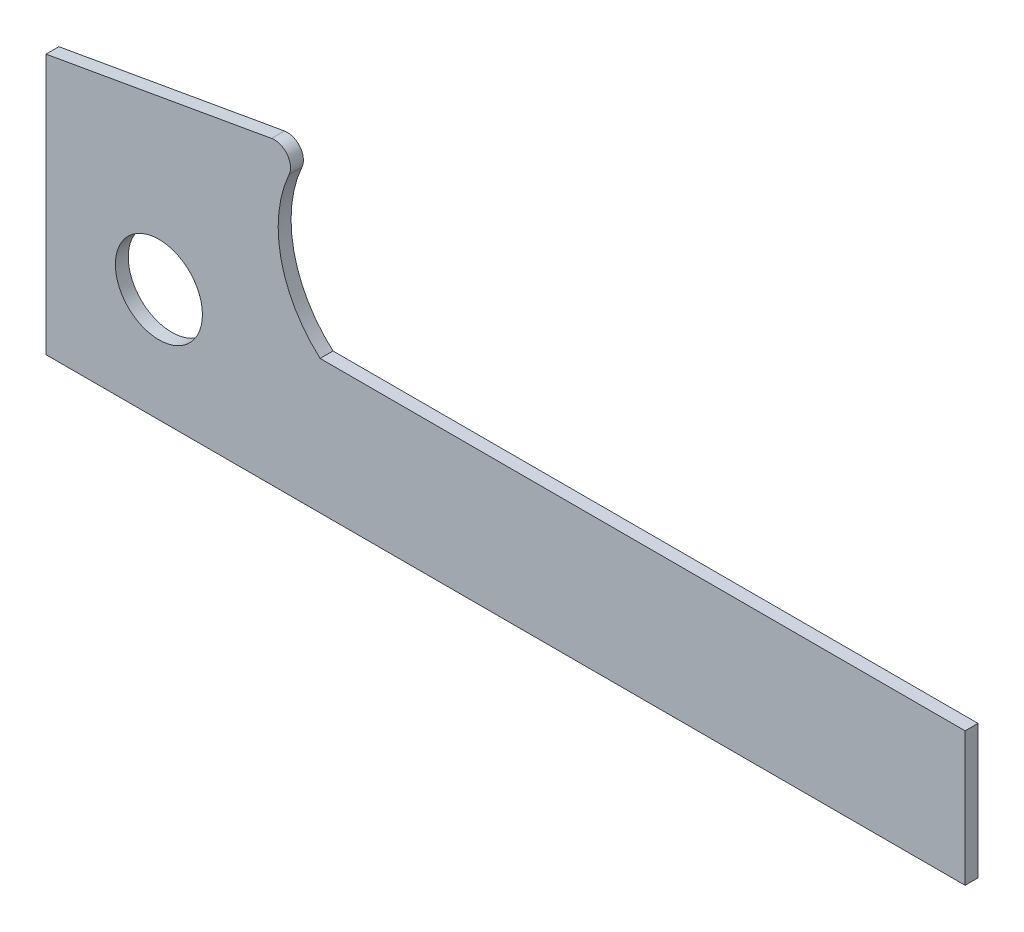
SolidWorks part; units mm, degrees
material "AISI 1020"
ref_plane "Спереди" through (0, 0, 0) normal (0, 0, 1) x (1, 0, 0)
ref_plane "Сверху" through (0, 0, 0) normal (0, 1, 0) x (1, 0, 0)
ref_plane "Справа" through (0, 0, 0) normal (1, 0, 0) x (0, 0, -1)
sketch "Эскиз1" plane through (0, 0, 0) normal (0, 0, 1) x (1, 0, 0)
  line L0 (0, -35) -> (0, 35) construction
  line L1 (0, -35) -> (250, -35)
  line L2 (-35, -35) -> (-35, 45.7214)
  line L4 (250, -35) -> (250, 6.5)
  line L5 (0, 0) -> (40.5631, 44.0234) construction
  line L6 (-17.2764, -30.4389) -> (17.2764, 30.4389) construction
  line L8 (-35, -35) -> (-35, -40) construction
  line L9 (-35, -40) -> (250, -40) construction
  line L10 (250, -40) -> (250, -35) construction
  line L12 (-35, -35) -> (0, -35)
  line L13 (200.1444, -153.8415) -> (-17.2764, -30.4389) construction
  line L14 (58.4892, 12.7455) -> (43.6208, 25) construction
  line L15 (43.6208, 25) -> (40.5631, 44.0234) construction
  line L16 (0, 0) -> (58.4892, 12.7455) construction
  line L17 (0, 0) -> (43.6208, 25) construction
  line L18 (0, 0) -> (43.6208, 25) construction
  line L19 (50, 6.5) -> (110, 6.5) construction
  line L20 (-35, 45.7214) -> (34.9487, 58.0553)
  line L21 (-1450, 65) -> (100, 65) construction
  line L22 (50, 6.5) -> (250, 6.5)
  circle A0 centre (40.5631, 44.0234) radius 2.5 construction
  circle A1 centre (43.6208, 25) radius 2.5 construction
  arc A2 (50, 6.5) -> (40.3761, 51.0784) centre (75.3946, 35.3104) cw
  arc A3 (40.3761, 51.0784) -> (34.9487, 58.0553) centre (35.8169, 53.1312) ccw
  circle A4 centre (0, 0) radius 13.5 construction
  circle A5 centre (0, 0) radius 13.5
  point P9 (0, 0)
  point P39 (45.9778, 60)
  dimension "D3" = 5
  dimension "D4" = 5
  dimension "D1" = 5
  dimension "D2" = 5
  dimension "100" = 100
base flange "Базовая кромка1" sketch "Эскиз1" thickness 4 reverse thickness direction no parameters "D1"=0.74
sketch "Сгиб-Линии1" [suppressed] plane through (0, 0, 0) normal (0, 1, 0) x (1, 0, 0)
sketch "Граничная рамка1" [suppressed] plane through (0, 0, 0) normal (0, 1, 0) x (1, 0, 0)
sheet metal parameters "Листовой металл3" thickness 4 parameters "D1"=0.74
flat pattern "Развертка3" [suppressed]
sketch "Сгиб-Линии2" plane through (0, 0, 0) normal (0, 1, 0) x (1, 0, 0)
sketch3d "Граничная рамка2" [suppressed]
  line L0 (-110.3946, 22.8207, 0) -> (174.6054, 22.8207, 0) construction
  line L1 (-110.3946, -70.3104, 0) -> (174.6054, -70.3104, 0) construction
  line L2 (-110.3946, 22.8207, 0) -> (-110.3946, -70.3104, 0) construction
  line L3 (174.6054, 22.8207, 0) -> (174.6054, -70.3104, 0) construction
